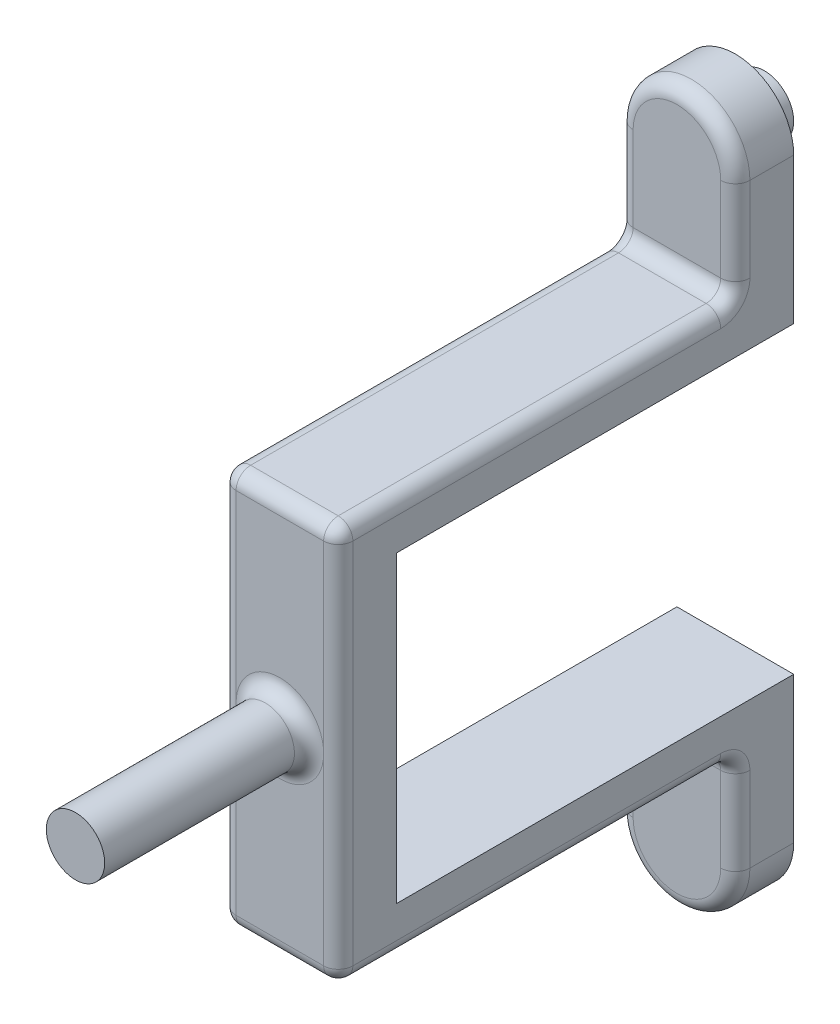
SolidWorks part; units mm, degrees
ref_plane "Front Plane" through (0, 0, 0) normal (0, 0, 1) x (1, 0, 0)
ref_plane "Top Plane" through (0, 0, 0) normal (0, 1, 0) x (1, 0, 0)
ref_plane "Right Plane" through (0, 0, 0) normal (1, 0, 0) x (0, 0, -1)
sketch "Sketch1" plane through (0, 0, 0) normal (0, 0, 1) x (1, 0, 0)
  line L0 (-82.5745, 54.3283) -> (-82.5745, 54.5823) construction
  line L1 (-83.8407, 73.8863) -> (-78.7607, 73.8863)
  line L2 (-83.8407, 73.8863) -> (-83.8407, 67.5363)
  line L3 (-83.8407, 67.5363) -> (-78.7607, 67.5363)
  line L4 (-78.7607, 73.8863) -> (-78.7607, 67.5363)
  line L6 (-95.4807, 60.9323) -> (-67.1207, 60.9323) construction
  line L7 (-83.8407, 69.5683) -> (-78.7607, 69.5683)
  line L8 (-83.8407, 52.2963) -> (-78.7607, 52.2963)
  line L9 (-83.8407, 54.3283) -> (-78.7607, 54.3283)
  line L10 (-78.7607, 47.9783) -> (-78.7607, 54.3283)
  line L11 (-83.8407, 47.9783) -> (-78.7607, 47.9783)
  line L12 (-83.8407, 47.9783) -> (-83.8407, 54.3283)
  line L13 (-81.3007, 67.5363) -> (-81.3007, 54.3283) construction
  line L14 (-82.5745, 67.2823) -> (-82.5745, 67.5363)
  circle A0 centre (-81.3007, 73.8863) radius 2.54
  circle A1 centre (-81.3007, 47.9783) radius 2.54
  point P4 (-81.3007, 60.9323)
  point P7 (-81.3007, 60.9323)
  dimension "D2" = 5.08
  dimension "D1" = 2.032
  dimension "D3" = 6.35
  dimension "D4" = 0.254
  dimension "D5" = 13.208
extrude "Boss-Extrude1" add sketch "Sketch1" along normal blind 2.54 contours A0 L2 L7 L4 | L1 A0 | L1 A0 | A1 L11 | A1 L11 | L12 A1 L10 L8 region at (-81.3007, 74.9643, 0) region at (-81.3007, 70.7991, 0) region at (-81.3007, 72.8083, 0) region at (-81.3007, 51.0656, 0) region at (-81.3007, 49.0563, 0) region at (-81.3007, 46.9003, 0)
extrude "Boss-Extrude2" add sketch "Sketch1<7>" along normal blind 17.272 contours L12 L8 L10 L9 | L7 L2 L3 L4 region at (-81.3007, 68.5523, 0) region at (-81.3007, 53.3123, 0)
sketch "Sketch1<7>" plane through (0, 0, 0) normal (0, 0, 1) x (1, 0, 0) same geometry as "Sketch1"
sketch "Sketch2" plane through (0, 0, 17.272) normal (0, 0, 1) x (1, 0, 0)
  line L1 (-83.8407, 69.5683) -> (-78.7607, 69.5683)
  line L2 (-83.8407, 69.5683) -> (-83.8407, 52.2963)
  line L3 (-83.8407, 52.2963) -> (-78.7607, 52.2963)
  line L4 (-78.7607, 69.5683) -> (-78.7607, 52.2963)
extrude "Boss-Extrude3" add sketch "Sketch2" along normal blind 2.54 contours L2 L1 L4 L3
sketch "Sketch3" plane through (0, 0, 19.812) normal (0, 0, 1) x (1, 0, 0)
  line L0 (-83.8407, 60.9323) -> (-78.7607, 60.9323) construction
  line L1 (-83.8407, 69.5683) -> (-83.8407, 52.2963) construction
  line L2 (-78.7607, 69.5683) -> (-78.7607, 52.2963) construction
  circle A0 centre (-81.3007, 60.9323) radius 1.27
  point P8 (-81.3007, 60.9323)
  dimension "D1" = 2.54
extrude "Boss-Extrude4" add sketch "Sketch3" along normal blind 8.89
fillet "Fillet1" radius 0.635 17 edges at (-83.8407, 50.1373, 2.54) (-81.3007, 45.4383, 2.54) (-83.8407, 71.7273, 2.54) (-81.3007, 76.4263, 2.54) (-83.8407, 60.9323, 19.812) (-78.7607, 50.1373, 2.54) (-78.7607, 60.9323, 19.812) (-78.7607, 71.7273, 2.54) (-78.7607, 69.5683, 11.176) (-81.3007, 69.5683, 19.812) (-83.8407, 69.5683, 11.176) (-81.3007, 69.5683, 2.54) (-81.3007, 52.2963, 19.812) (-78.7607, 52.2963, 11.176) (-81.3007, 52.2963, 2.54) (-83.8407, 52.2963, 11.176) (-82.5707, 60.9323, 19.812)
sketch "Sketch4" plane through (0, 0, 0) normal (0, 0, -1) x (-1, 0, 0)
  circle A0 centre (81.3007, 73.8863) radius 1.27
  circle A1 centre (81.3007, 47.9783) radius 1.27
  dimension "D1" = 2.54
extrude "Boss-Extrude5" add sketch "Sketch4" along normal blind 1.27 contours A0 | A1
